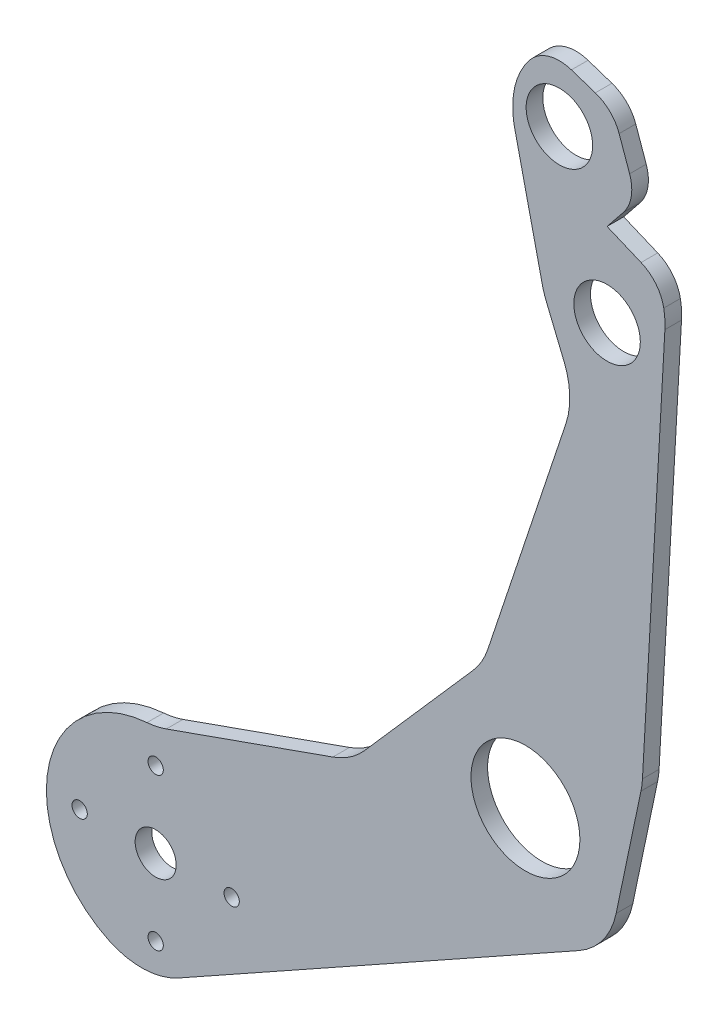
SolidWorks part; units mm, degrees
ref_plane "Front Plane" through (0, 0, 0) normal (0, 0, 1) x (1, 0, 0)
ref_plane "Top Plane" through (0, 0, 0) normal (0, 1, 0) x (1, 0, 0)
ref_plane "Right Plane" through (0, 0, 0) normal (1, 0, 0) x (0, 0, -1)
sketch "Sketch1" plane through (0, 0, 0) normal (0, 0, 1) x (1, 0, 0)
  line L0 (198.8616, 69.616) -> (188.9649, 57.2856)
  line L1 (38.107, -163.0696) -> (103.5814, -139.8861)
  line L2 (103.5814, -139.8861) -> (147.5504, -89.7457)
  line L3 (147.5504, -89.7457) -> (171.8362, -16.8147)
  line L4 (171.8362, -16.8147) -> (178.1894, 2.2642)
  line L5 (178.1894, 2.2642) -> (167.83, 27.4472)
  line L6 (157.4706, 73.0101) -> (157.4706, 93.39)
  line L7 (157.4706, 93.39) -> (170.6001, 98.791)
  line L8 (170.6001, 98.791) -> (190.928, 92.0219)
  line L9 (190.928, 92.0219) -> (198.8616, 69.616)
  line L10 (208.5808, 42.1673) -> (200.6841, -98.6168)
  line L11 (200.6841, -98.6168) -> (189.6112, -151.3856)
  line L12 (189.6112, -151.3856) -> (38.107, -236.12)
  line L13 (188.9649, 57.2856) -> (205.7114, 50.2708)
  line L14 (205.7114, 50.2708) -> (208.5808, 42.1673)
  line L15 (157.4706, 73.0101) -> (167.83, 27.4472)
  arc A9 (38.107, -163.0696) -> (38.107, -236.12) centre (38.107, -199.5948) ccw
  circle A10 centre (38.107, -199.5948) radius 6.8612
  circle A11 centre (161.6863, -124.719) radius 18.2009
  circle A12 centre (188.9649, 29.3961) radius 11.1125
  circle A13 centre (173.036, 78.2376) radius 11.1125
  circle A14 centre (38.107, -174.1948) radius 2.5527
  circle A15 centre (63.507, -199.5948) radius 2.5527
  circle A16 centre (38.107, -224.9948) radius 2.5527
  circle A17 centre (12.707, -199.5948) radius 2.5527
  arc A18 (208.5805, 42.2939) -> (199.2278, 54.4816) centre (195.8806, 42.2306) ccw construction
  arc A19 (208.5405, 40.7376) -> (208.5805, 42.2939) centre (183.1808, 42.1673) ccw construction
  point P25 (-7.2428, -159.1538)
  point P26 (38.107, -199.5948)
  point P33 (38.107, -199.5948)
  point P34 (161.8563, -124.634)
  point P37 (161.6863, -124.719)
  point P38 (188.9649, 29.3961)
  point P39 (205.6119, 53.3431)
  point P43 (197.7472, 68.2275)
  point P44 (188.9649, 57.2856)
  point P45 (205.7283, 53.0237)
  point P46 (103.5814, -139.8861)
  point P47 (208.5808, 42.1673)
  dimension "D1" = 22.225
  dimension "D2" = 22.225
  dimension "D3" = 4
  dimension "D4" = 25.4
  dimension "D5" = 73.0504
extrude "Boss-Extrude1" add sketch "Sketch1" along normal blind 5.5562
fillet "Fillet1" radius 25.4 11 edges at (157.4706, 93.39, 2.7781) (157.4706, 73.0101, 2.7781) (167.83, 27.4472, 2.7781) (178.1894, 2.2642, 2.7781) (147.5504, -89.7457, 2.7781) (103.5814, -139.8861, 2.7781) (38.107, -163.0696, 2.7781) (38.107, -236.12, 2.7781) (189.6112, -151.3856, 2.7781) (200.6841, -98.6168, 2.7781) (208.5808, 42.1673, 2.7781)
fillet "Fillet3" radius 12.7 2 edges at (190.928, 92.0219, 2.7781) (170.6001, 98.791, 2.7781)
fillet "Fillet4" radius 12.7 2 edges at (205.7114, 50.2708, 2.7781) (198.8616, 69.616, 2.7781)
